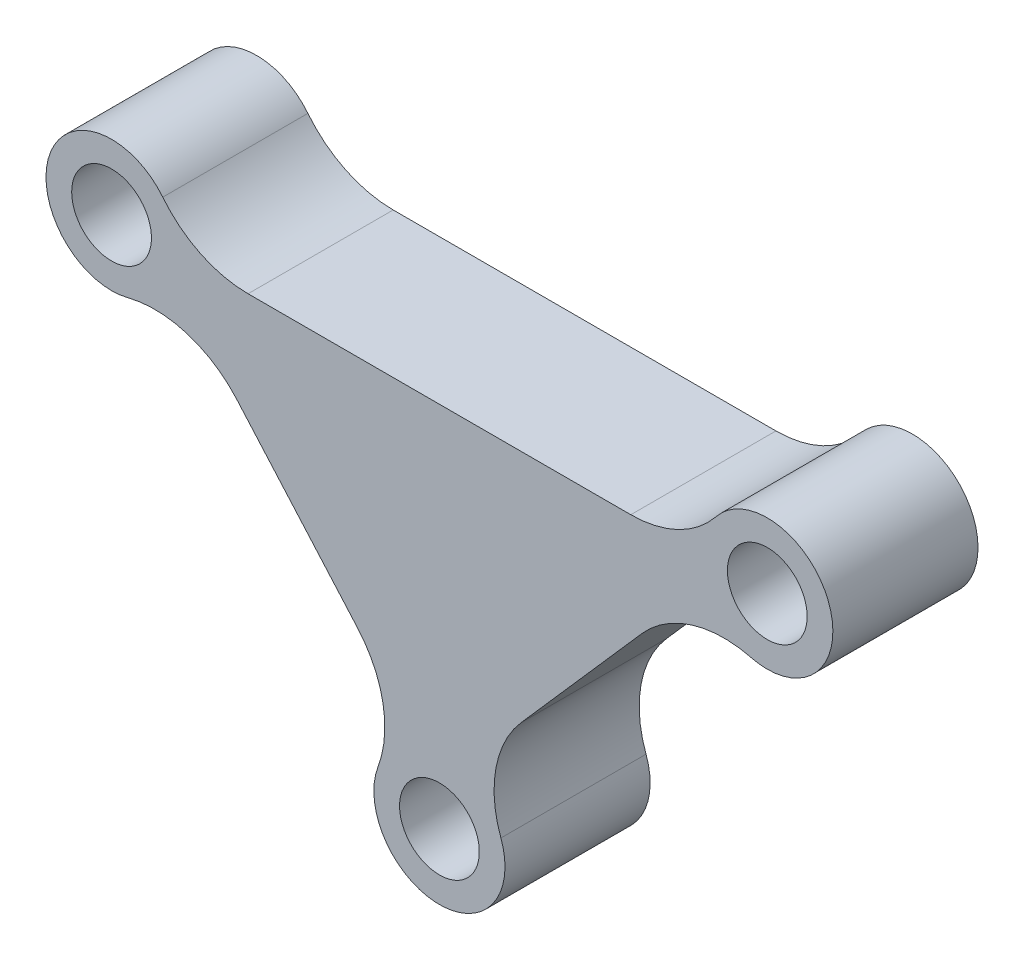
SolidWorks part; units mm, degrees
ref_plane "Plan de face" through (0, 0, 0) normal (0, 0, 1) x (1, 0, 0)
ref_plane "Plan de dessus" through (0, 0, 0) normal (0, 1, 0) x (1, 0, 0)
ref_plane "Plan de droite" through (0, 0, 0) normal (1, 0, 0) x (0, 0, -1)
sketch "Esquisse2" plane through (0, 0, 0) normal (0, 0, 1) x (1, 0, 0)
  line L0 (-13.175, 10) -> (13.175, 10)
  line L1 (13.175, 10) -> (0, -5)
  line L2 (0, -5) -> (-13.175, 10)
  line L3 (0, 0) -> (-13.175, 10) construction
  line L4 (0, 0) -> (13.175, 10) construction
  circle A0 centre (-15, 10) radius 3
  circle A1 centre (-15, 10) radius 1.825
  circle A2 centre (15, 10) radius 3
  circle A3 centre (15, 10) radius 1.825
  circle A4 centre (0, -6.825) radius 3
  circle A5 centre (0, -6.825) radius 1.825
  dimension "D2" = 3.65
  dimension "D3" = 6
  dimension "D1" = 5
  dimension "D4" = 10
  dimension "D5" = 15
extrude "Boss.-Extru.1" add sketch "Esquisse2" along normal blind 6.64 contours A4 L1 A2 L0 A0 L2 | L1 A5 L2 A4 | L1 A4 L2 | A3 | A1 | L0 L1 L2 | A2 | A0 | A4 | A5 region at (-15, 10, 0) region at (0, 5.0202, 0) region at (15, 10, 0) region at (0, -4.2487, 0) region at (-0.5172, -4.5383, 0)
fillet "Congé1" radius 5 6 edges at (-12, 10, 3.32) (-12.2089, 8.9001, 3.32) (-0.9084, -3.9658, 3.32) (12.2089, 8.9001, 3.32) (12, 10, 3.32) (0.9084, -3.9658, 3.32)
